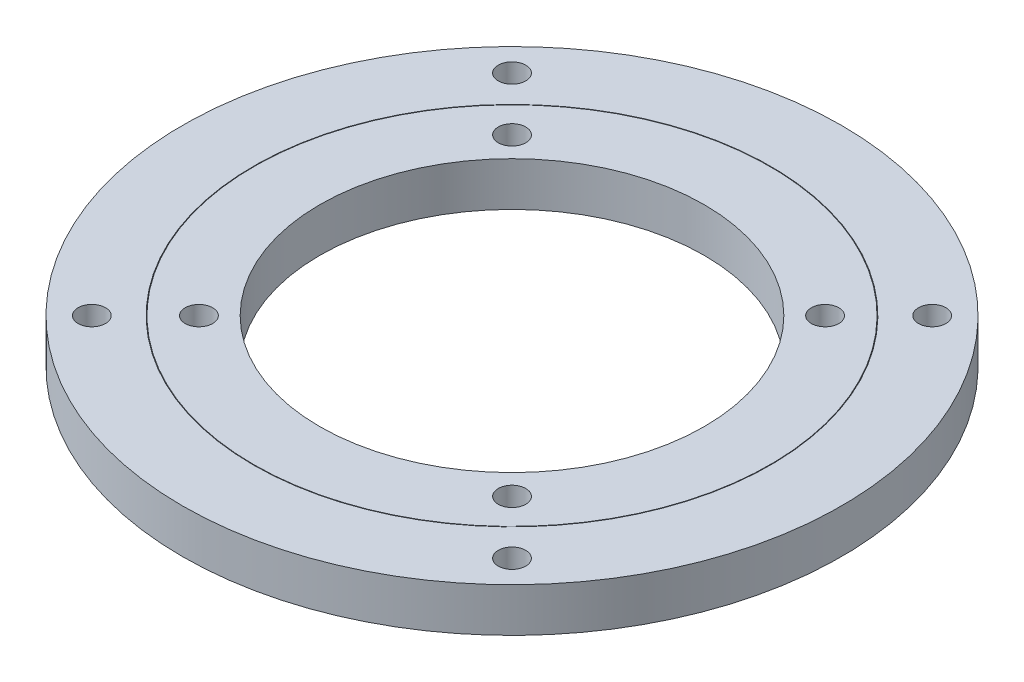
SolidWorks part; units mm, degrees
note: The reader was unsure of these and kept them because the rebuilt part matched: shared geometry of "Sketch1<4>".
ref_plane "Front Plane" through (0, 0, 0) normal (0, 0, 1) x (1, 0, 0)
ref_plane "Top Plane" through (0, 0, 0) normal (0, 1, 0) x (1, 0, 0)
ref_plane "Right Plane" through (0, 0, 0) normal (1, 0, 0) x (0, 0, -1)
sketch "Sketch1" plane through (0, 0, 0) normal (0, 1, 0) x (1, 0, 0)
  line L0 (0, 38.25) -> (0, -38.25) construction
  line L1 (-28.5, 28.5) -> (28.5, 28.5) construction
  line L2 (-28.5, 28.5) -> (-28.5, -28.5) construction
  line L3 (-28.5, -28.5) -> (28.5, -28.5) construction
  line L4 (28.5, 28.5) -> (28.5, -28.5) construction
  line L5 (-28.5, 28.5) -> (28.5, -28.5) construction
  line L6 (-28.5, -28.5) -> (28.5, 28.5) construction
  line L7 (-38.25, 38.25) -> (38.25, 38.25) construction
  line L8 (0, 0) -> (112.7341, 0) construction
  circle A0 centre (0, 0) radius 35
  circle A1 centre (0, 0) radius 47
  circle A2 centre (0, 0) radius 60
  circle A3 centre (-38.25, 38.25) radius 2.5
  circle A4 centre (38.25, 38.25) radius 2.5
  circle A5 centre (28.5, 28.5) radius 2.5
  circle A6 centre (-28.5, 28.5) radius 2.5
  circle A7 centre (38.25, -38.25) radius 2.5
  circle A8 centre (28.5, -28.5) radius 2.5
  circle A9 centre (-28.5, -28.5) radius 2.5
  circle A10 centre (-38.25, -38.25) radius 2.5
  circle A11 centre (0, 0) radius 47.1
  point P12 (0, 0)
  point P15 (0, 38.25)
  dimension "D1" = 120
  dimension "D2" = 94
  dimension "D3" = 70
  dimension "D7" = 5
  dimension "D8" = 94.2
  dimension "D4" = 57
  dimension "D5" = 76.5
  dimension "D6" = 76.5
extrude "Boss-Extrude2" add sketch "Sketch1" along normal blind 8 contours A1 A8 A6 A5 A0 A9
extrude "Boss-Extrude3" add sketch "Sketch1<4>" along normal blind 8 contours A2 A7 A4 A3 A1 A10
sketch "Sketch1<4>" plane through (0, 0, 0) normal (0, 1, 0) x (1, 0, 0) same geometry as "Sketch1"
sketch "Sketch3" plane through (0, 8, 0) normal (0, 1, 0) x (1, 0, 0)
  circle A0 centre (-28.5, 28.5) radius 4.65
  circle A1 centre (-28.5, -28.5) radius 4.65
  circle A2 centre (28.5, -28.5) radius 4.65
  circle A3 centre (28.5, 28.5) radius 4.65
  dimension "D1" = 9.3
